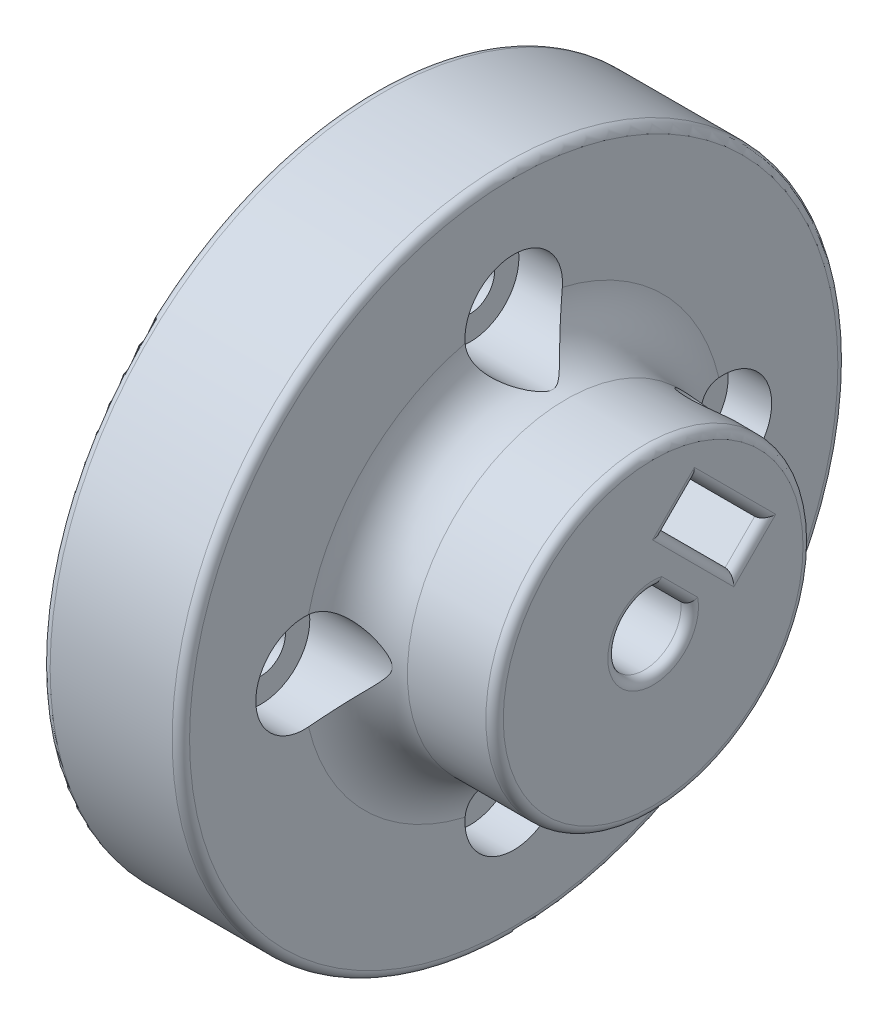
SolidWorks part; units mm, degrees
ref_plane "Front Plane" through (0, 0, 0) normal (0, 0, 1) x (1, 0, 0)
ref_plane "Top Plane" through (0, 0, 0) normal (0, 1, 0) x (1, 0, 0)
ref_plane "Right Plane" through (0, 0, 0) normal (1, 0, 0) x (0, 0, -1)
sketch "Sketch2" plane through (0, 0, 0) normal (0, 0, 1) x (1, 0, 0)
  line L0 (0, 2.1) -> (-16, 2.1)
  line L1 (0, 2.1) -> (0, 9.1)
  line L2 (0, 9.1) -> (-8, 9.1)
  line L3 (-8, 9.1) -> (-8, 19.1)
  line L4 (-8, 19.1) -> (-16, 19.1)
  line L5 (-16, 19.1) -> (-16, 2.1)
  line L7 (0, 0) -> (-15.3242, 0) construction
  dimension "D1" = 4.2
  dimension "D2" = 7
  dimension "D3" = 8
  dimension "D4" = 8
  dimension "D5" = 10
revolve "Revolve1" add sketch "Sketch2" angle 360 about L7
sketch "Sketch3" plane through (-8, 0, 0) normal (1, 0, 0) x (0, 0, -1)
  circle A0 centre (0, 0) radius 12 construction
  circle A1 centre (0, 12) radius 1.4
  circle A2 centre (12, 0) radius 1.4
  circle A3 centre (0, -12) radius 1.4
  circle A4 centre (-12, 0) radius 1.4
  dimension "D1" = 24
  dimension "D2" = 2.8
extrude "Cut-Extrude1" cut sketch "Sketch3" against normal up to next
sketch "Sketch4" plane through (-8, 0, 0) normal (1, 0, 0) x (0, 0, -1)
  circle A0 centre (-12, 0) radius 2.8
  circle A1 centre (0, 12) radius 2.8
  circle A2 centre (12, 0) radius 2.8
  circle A3 centre (0, -12) radius 2.8
  dimension "D1" = 5.6
extrude "Cut-Extrude2" cut sketch "Sketch4" against normal blind 2.5
sketch "Sketch5" plane through (0, 0, 0) normal (1, 0, 0) x (0, 0, -1)
  line L0 (2.0853, 0.2482) -> (0.2482, 2.0853)
  line L1 (0, 0) -> (4.2951, 0) construction
  circle A0 centre (0, 0) radius 2.1 construction
  arc A1 (0.2482, 2.0853) -> (2.0853, 0.2482) centre (0, 0) cw
  dimension "D1" = 1.65
  dimension "D2" = 45
extrude "Boss-Extrude1" add sketch "Sketch5" against normal up to surface (16 mm away) up to face at (-16, 12, 1.4)
ref_plane "Plane1" through (0, 2.6517, -2.6517) normal (0, -0.7071, 0.7071) x (-1, 0, 0)
sketch "Sketch6" plane through (0, 2.6517, -2.6517) normal (0, -0.7071, 0.7071) x (-1, 0, 0)
  line L0 (0, 0) -> (6.5937, 0) construction
  line L1 (0, 9.1) -> (0, -9.1) construction
  circle A0 centre (3.2, 0) radius 1.6
  dimension "D1" = 3.2
  dimension "D2" = 3.2
extrude "Cut-Extrude3" cut sketch "Sketch6" against normal through all and the other way up to next
sketch "Sketch7" plane through (0, 2.6517, -2.6517) normal (0, -0.7071, 0.7071) x (-1, 0, 0)
  line L0 (1.5834, 2.8) -> (0, 2.8)
  line L1 (6.4332, 0) -> (4.8166, 2.8)
  line L2 (4.8166, 2.8) -> (1.5834, 2.8)
  line L3 (1.5834, 2.8) -> (0.7751, 1.4) construction
  line L4 (-0.0332, 0) -> (0.7751, -1.4) construction
  line L5 (1.5834, -2.8) -> (4.8166, -2.8)
  line L6 (4.8166, -2.8) -> (6.4332, 0)
  line L7 (0, 9.1) -> (0, -9.1) construction
  line L8 (1.5834, -2.8) -> (0, -2.8)
  line L9 (0, -2.8) -> (0, 2.8)
  line L10 (0.7751, -1.4) -> (1.5834, -2.8) construction
  line L11 (0.7751, 1.4) -> (-0.0332, 0) construction
  circle A0 centre (3.2, 0) radius 2.8 construction
  dimension "D1" = 5.6
extrude "Cut-Extrude4" cut sketch "Sketch7" against normal blind 2.4
fillet "Fillet1" radius 0.5 7 edges at (0, 2.6517, -2.6517) (0, 1.5203, -5.4801) (0, 4.3487, -4.3487) (0, 5.4801, -1.5203) (0, 1.1667, -1.1667) (0, -1.4849, 1.4849) (0, 0, -9.1)
fillet "Fillet2" radius 3 1 edges at (-8, 0, -9.1)
fillet "Fillet3" radius 0.5 2 edges at (-16, 0, -19.1) (-8, 0, -19.1)
